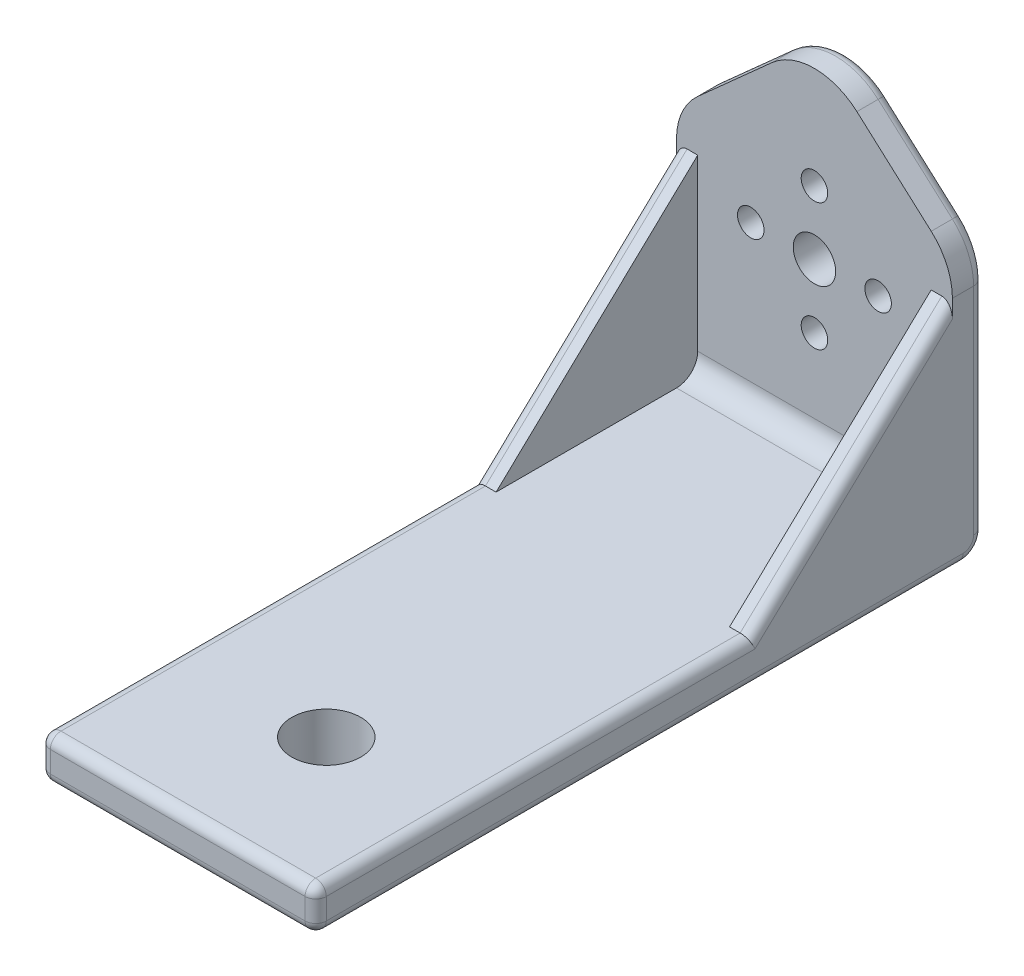
SolidWorks part; units mm, degrees
ref_plane "Front Plane" through (0, 0, 0) normal (0, 0, 1) x (1, 0, 0)
ref_plane "Top Plane" through (0, 0, 0) normal (0, 1, 0) x (1, 0, 0)
ref_plane "Right Plane" through (0, 0, 0) normal (1, 0, 0) x (0, 0, -1)
sketch "Sketch1" plane through (0, 0, 0) normal (0, 0, 1) x (1, 0, 0)
  line L0 (0, 11.4628) -> (0, -12.0557) construction
  line L1 (-13.1568, 0) -> (14.2861, 0) construction
  line L2 (-13, -2.6826) -> (-13, -25)
  line L3 (-11.0009, 1.7888) -> (-4.0009, 8.0523)
  line L4 (13, -2.6826) -> (13, -25)
  line L5 (11.0009, 1.7888) -> (4.0009, 8.0523)
  line L6 (-13, -25) -> (13, -25)
  circle A0 centre (0, 0) radius 1.25
  circle A4 centre (0, -6) radius 2
  arc A5 (13, -2.6826) -> (11.0009, 1.7888) centre (7, -2.6826) ccw
  arc A6 (4.0009, 8.0523) -> (-4.0009, 8.0523) centre (0, 3.5809) ccw
  arc A7 (-13, -2.6826) -> (-11.0009, 1.7888) centre (-7, -2.6826) cw
  circle A8 centre (6, -6) radius 1.25
  circle A9 centre (0, -12) radius 1.25
  circle A10 centre (-6, -6) radius 1.25
  point P18 (0, 0)
  point P23 (13, 0)
  point P26 (0, 11.6322)
  point P29 (-13, 0)
  point P39 (0, -6)
  dimension "D1" = 2.5
  dimension "D2" = 4
  dimension "D6" = 6
  dimension "D8" = 4
  dimension "D5" = 26
  dimension "D7" = 25
extrude "Boss-Extrude1" add sketch "Sketch1" along normal blind 3
sketch "Sketch2" plane through (0, 0, 3) normal (0, 0, 1) x (1, 0, 0)
  line L0 (13, -25) -> (13, -2.6826) construction
  line L1 (-13, -25) -> (13, -25)
  line L2 (-13, -25) -> (-13, -21)
  line L3 (-13, -21) -> (13, -21)
  line L4 (13, -25) -> (13, -21)
  dimension "D1" = 4
extrude "Boss-Extrude2" add sketch "Sketch2" along normal blind 60
sketch "Sketch3" plane through (0, -21, 0) normal (0, 1, 0) x (1, 0, 0)
  line L0 (13, -63) -> (13, -3) construction
  line L2 (13, -3) -> (-13, -3) construction
  circle A0 centre (1, -50) radius 3.25
  dimension "D1" = 6.5
  dimension "D2" = 12
  dimension "D3" = 47
extrude "Cut-Extrude1" cut sketch "Sketch3" against normal through all
sketch "Sketch4" plane through (0, -25, 0) normal (0, -1, 0) x (1, 0, 0)
  line L4 (-13, 0) -> (13, 0)
  line L5 (13, 0) -> (13, 63)
  line L6 (13, 63) -> (-13, 63)
  line L7 (-13, 63) -> (-13, 0)
  line L8 (-13, 0) -> (13, 0)
  line L9 (13, 0) -> (13, 63)
  line L10 (13, 63) -> (-13, 63)
  line L11 (-13, 63) -> (-13, 0)
  circle A0 centre (1, 50) radius 3.25 construction
  circle A1 centre (1, 50) radius 3.25
  circle A2 centre (1, 50) radius 8
  circle M6 centre (1, 50) radius 3.25
  dimension "D2" = 16
  dimension "D1" = 0
extrude "Boss-Extrude3" add sketch "Sketch4" along normal blind 1 contours A2 M6 region at (-6.7737, -25, 50)
sketch "Sketch5" plane through (0, -25, 0) normal (0, -1, 0) x (1, 0, 0)
  line L0 (-13, 10) -> (13, 10) construction
  line L1 (-13, 63) -> (-13, 0) construction
  line L2 (13, 63) -> (13, 0) construction
  line L3 (-13, 0) -> (13, 0) construction
  line L4 (0, 16.476) -> (0, 4.5805) construction
  circle A0 centre (-7.5, 10) radius 1.5
  circle A1 centre (7.5, 10) radius 1.5
  dimension "D2" = 3
  dimension "D1" = 10
  dimension "D3" = 15
extrude "Boss-Extrude4" add sketch "Sketch5" along normal blind 3
sketch "Sketch6" plane through (-13, 0, 0) normal (-1, 0, 0) x (0, 0, 1)
  line L0 (0, -3) -> (3, -3)
  line L1 (0, -2.6826) -> (0, -25) construction
  line L2 (3, -2.6826) -> (3, -21) construction
  line L3 (3, -3) -> (22, -21)
  line L4 (63, -21) -> (3, -21) construction
  line L5 (22, -21) -> (22, -25)
  line L6 (63, -25) -> (0, -25) construction
  line L7 (22, -25) -> (0, -25)
  line L8 (0, -25) -> (0, -3)
  dimension "D1" = 22
  dimension "D2" = 22
extrude "Boss-Extrude5" add sketch "Sketch6" against normal blind 2
mirror "Mirror1" about plane through (0, 0, 0) normal (1, 0, 0) of "Boss-Extrude5"
fillet "Fillet1" radius 2 2 edges at (0, -21, 3) (0, -25, 0)
fillet "Fillet2" radius 1 19 edges at (13, -21, 42.5) (13, -25, 32.5) (13, -24.4142, 0.5858) (13, -12.8413, 0) (12.4775, -0.2336, 0) (7.5009, 4.9205, 0) (0, 9.5809, 0) (-7.5009, 4.9205, 0) (-12.4775, -0.2336, 0) (-13, -21, 42.5) (-13, -23, 63) (-13, -25, 32.5) (-13, -24.4142, 0.5858) (-13, -12.8413, 0) (0, -21, 63) (13, -23, 63) (0, -25, 63) (13, -12, 12.5) (-13, -12, 12.5)
fillet "Fillet3" radius 0.5 2 edges at (6, -28, 10) (-6, -28, 10)
